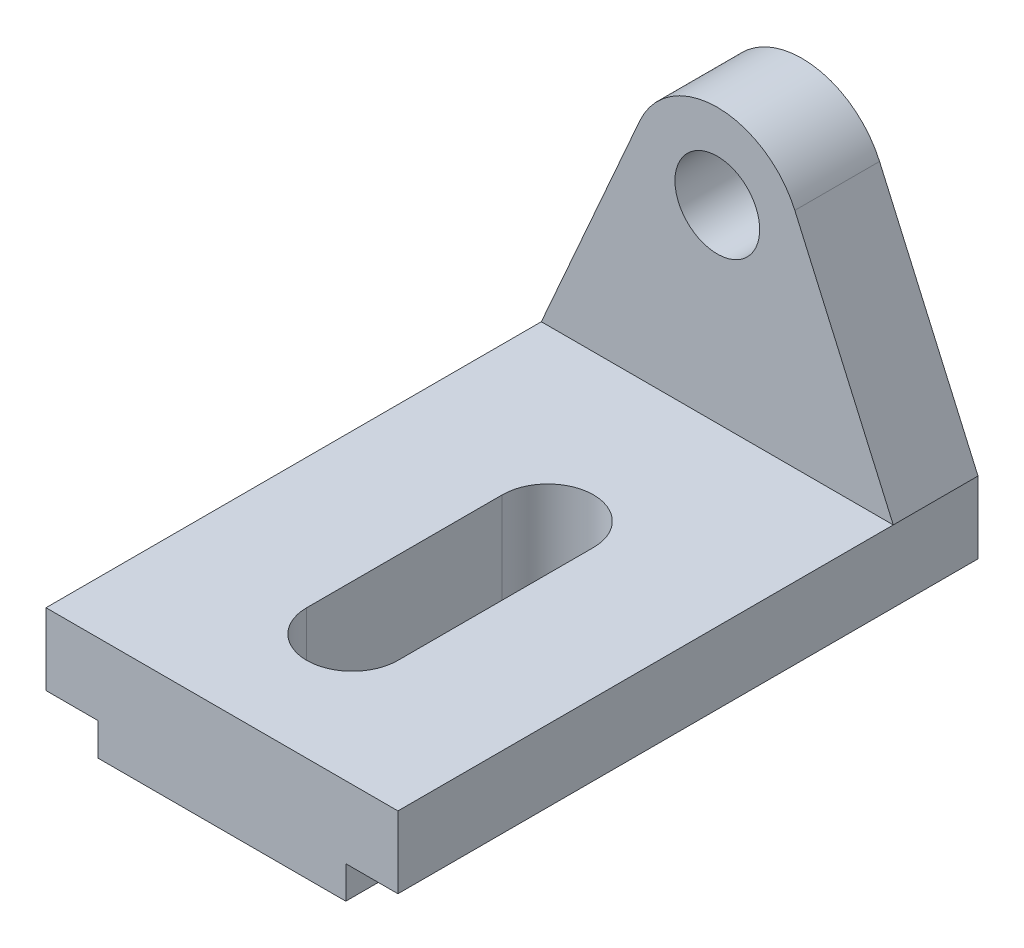
SolidWorks part; units mm, degrees
ref_plane "Plano frontal" through (0, 0, 0) normal (0, 0, 1) x (1, 0, 0)
ref_plane "Plano superior" through (0, 0, 0) normal (0, 1, 0) x (1, 0, 0)
ref_plane "Plano direito" through (0, 0, 0) normal (1, 0, 0) x (0, 0, -1)
sketch "Esboço1" plane through (0, 0, 0) normal (0, 0, 1) x (1, 0, 0)
  line L0 (0, 0) -> (54, 0)
  line L1 (0, 0) -> (0, -16)
  line L2 (0, -16) -> (54, -16)
  line L3 (54, 0) -> (54, -16)
  dimension "D1" = 16
  dimension "D2" = 54
extrude "Ressalto-extrusão2" add sketch "Esboço1" along normal blind 89
sketch "Esboço2" plane through (0, 0, 89) normal (0, 0, 1) x (1, 0, 0)
  line L0 (46, -11.0112) -> (54, -11.0112)
  line L1 (54, -16) -> (54, 0) construction
  line L2 (8, -11.0112) -> (0, -11.0112)
  line L3 (0, 0) -> (0, -16) construction
  line L4 (0, -16) -> (54, -16) construction
  line L8 (8, -16) -> (46, -16)
  line L9 (8, -16) -> (8, -11.0112)
  line L10 (8, -11.0112) -> (46, -11.0112)
  line L11 (46, -16) -> (46, -11.0112)
  line M9 (0, 0) -> (0, -16)
  line M10 (0, -16) -> (54, -16)
  line M11 (54, -16) -> (54, 0)
extrude "Corte-extrusão2" cut sketch "Esboço2" against normal blind 89 contours L9 L2 M10 M9 | L11 L0 M10 M11 region at (50, -13.5056, 89) region at (4, -13.5056, 89)
sketch "Esboço5" plane through (0, 0, 0) normal (0, 0, -1) x (-1, 0, 0)
  line L0 (-54, 0) -> (-27, 0)
  line L1 (-54, -11.0112) -> (-54, 0) construction
  line L2 (-54, 0) -> (0, 0) construction
  line L3 (-27, 0) -> (-27, 29)
  line L4 (-38.8943, 34.2464) -> (-54, 0)
  line L5 (0, 0) -> (-15.1057, 34.2464)
  arc A0 (-15.1057, 34.2464) -> (-38.8943, 34.2464) centre (-27, 29) ccw
  circle A1 centre (-27, 29) radius 6.5
  line M6 (0, 0) -> (-54, 0)
  dimension "D2" = 26
  dimension "D3" = 13
  dimension "D1" = 29
extrude "Ressalto-extrusão3" add sketch "Esboço5" against normal blind 13 contours A1 L5 A0 L4 M6 region at (45.8212, 16.8471, 0)
sketch "Esboço6" plane through (0, 0, 0) normal (0, 1, 0) x (1, 0, 0)
  line L0 (0, -89) -> (27, -89)
  line L1 (54, -89) -> (0, -89) construction
  line L4 (27, -39) -> (27, -69) construction
  line L5 (34, -39) -> (34, -69)
  line L6 (20, -39) -> (20, -69)
  arc A0 (34, -39) -> (20, -39) centre (27, -39) ccw
  arc A1 (20, -69) -> (34, -69) centre (27, -69) ccw
  point P5 (27, -54)
  dimension "D2" = 30
  dimension "D3" = 14
extrude "Corte-extrusão3" cut sketch "Esboço6" against normal blind 27 contours L6 A1 L5 A0 region at (27, 0, 54)
